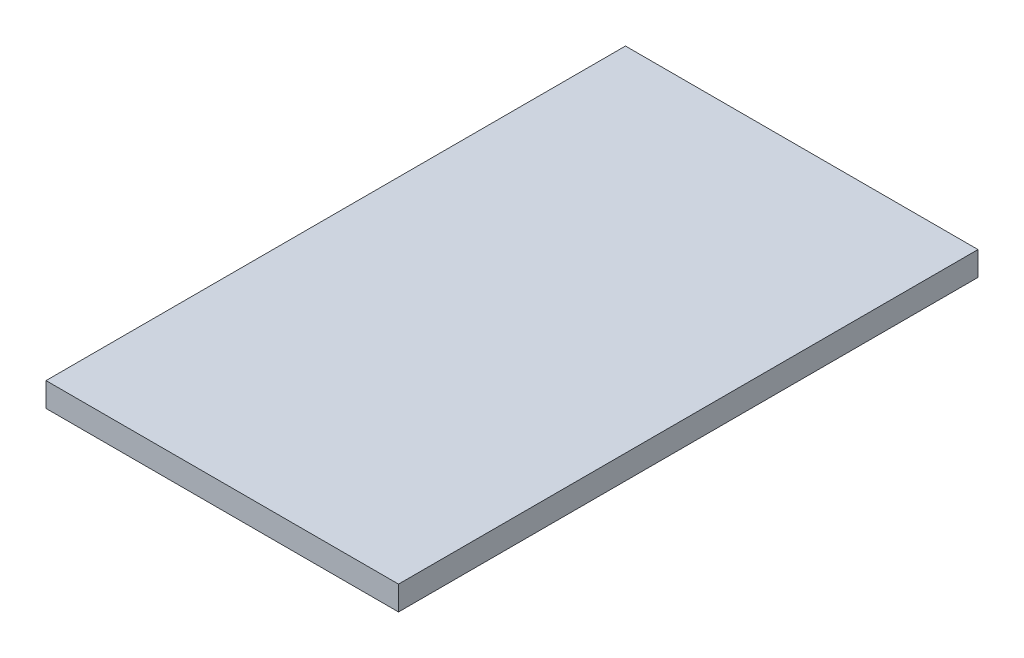
SolidWorks part; units mm, degrees
ref_plane "Front Plane" through (0, 0, 0) normal (0, 0, 1) x (1, 0, 0)
ref_plane "Top Plane" through (0, 0, 0) normal (0, 1, 0) x (1, 0, 0)
ref_plane "Right Plane" through (0, 0, 0) normal (1, 0, 0) x (0, 0, -1)
sketch "Sketch1" plane through (0, 0, 0) normal (0, 1, 0) x (1, 0, 0)
  line L1 (-36.5, -60) -> (36.5, -60)
  line L2 (-36.5, -60) -> (-36.5, 60)
  line L3 (-36.5, 60) -> (36.5, 60)
  line L4 (36.5, -60) -> (36.5, 60)
  line L5 (-36.5, -60) -> (36.5, 60) construction
  line L6 (-36.5, 60) -> (36.5, -60) construction
  point P0 (0, 0)
  dimension "D1" = 73
  dimension "D2" = 120
extrude "Boss-Extrude1" add sketch "Sketch1" along normal blind 5
